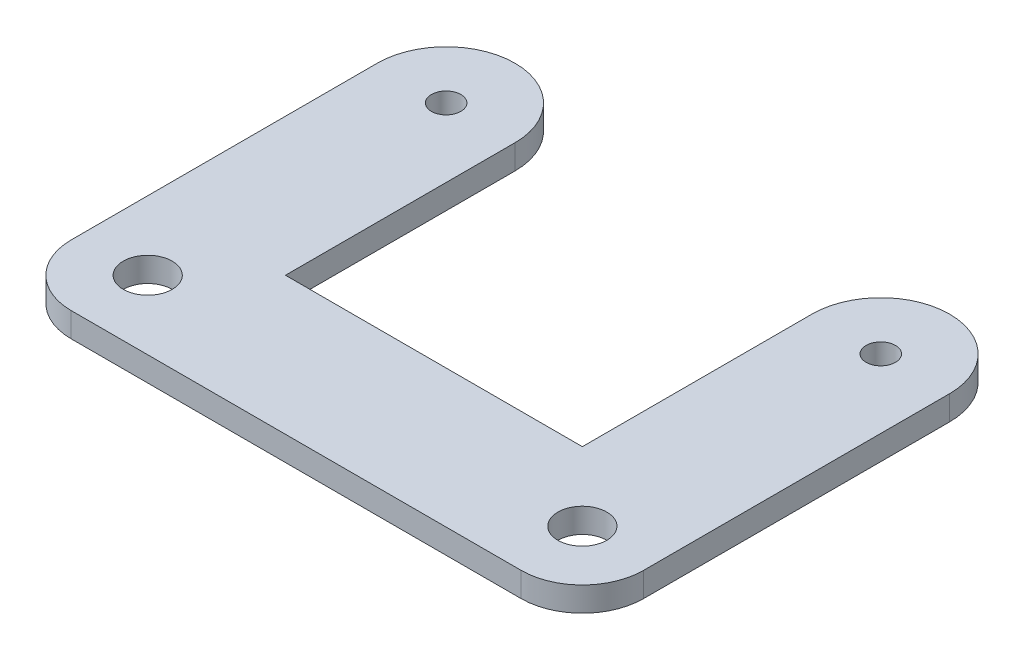
SolidWorks part; units mm, degrees
ref_plane "Front Plane" through (0, 0, 0) normal (0, 0, 1) x (1, 0, 0)
ref_plane "Top Plane" through (0, 0, 0) normal (0, 1, 0) x (1, 0, 0)
ref_plane "Right Plane" through (0, 0, 0) normal (1, 0, 0) x (0, 0, -1)
sketch "Sketch1" plane through (0, 0, 0) normal (0, 1, 0) x (1, 0, 0)
  line L0 (-33.1, 0) -> (-37.9, 0) construction
  line L1 (33.1, 0) -> (37.9, 0) construction
  line L2 (33.1, 0) -> (-33.1, 0) construction
  line L3 (-24.25, 0) -> (-24.25, -37.5)
  line L4 (-24.25, -37.5) -> (24.25, -37.5)
  line L5 (24.25, -37.5) -> (24.25, 0)
  line L6 (-46.75, 0) -> (-46.75, -60)
  line L7 (-46.75, -60) -> (46.75, -60)
  line L8 (46.75, -60) -> (46.75, 0)
  line L12 (-46.75, -60) -> (-24.25, -37.5) construction
  line L13 (24.25, -37.5) -> (46.75, -60) construction
  circle A0 centre (-35.5, 0) radius 2.4
  circle A2 centre (35.5, 0) radius 2.4
  circle A3 centre (-35.5, 0) radius 11.25
  circle A4 centre (35.5, 0) radius 11.25
  circle A5 centre (-35.5, -48.75) radius 4
  circle A6 centre (35.5, -48.75) radius 4
  dimension "D4" = 22.5
  dimension "D10" = 8
  dimension "D2" = 4.8
  dimension "D5" = 37.5
  dimension "D6" = 22.5
  dimension "D7" = 71
extrude "Boss-Extrude1" add sketch "Sketch1" along normal blind 4 contours A4 L5 L4 L3 A3 L6 L7 L8 A6 A5 | A3 A0 | A4 A2 region at (-35.5, 0, 10.9318) region at (0, 0, 38.6866) region at (35.5, 0, -10.9318)
fillet "Fillet1" radius 10 2 edges at (46.75, 2, 60) (-46.75, 2, 60)
equation "\"m3 hole\"= 3.2"
equation "\"m4 hole\"= 4.2"
equation "\"m5 hole\"= 5.2"
equation "\"m6 hole\"= 6.2"
equation "\"m8 hole\"= 8.2"
equation "\"m3 tapped\"= 2.5"
equation "\"m4 tapped\"= 3.3"
equation "\"m5 tapped\"= 4.2"
equation "\"m6 tapped\"= 5"
equation "\"m8 tapped\"= 6.8"
equation "\"e\"=10"
